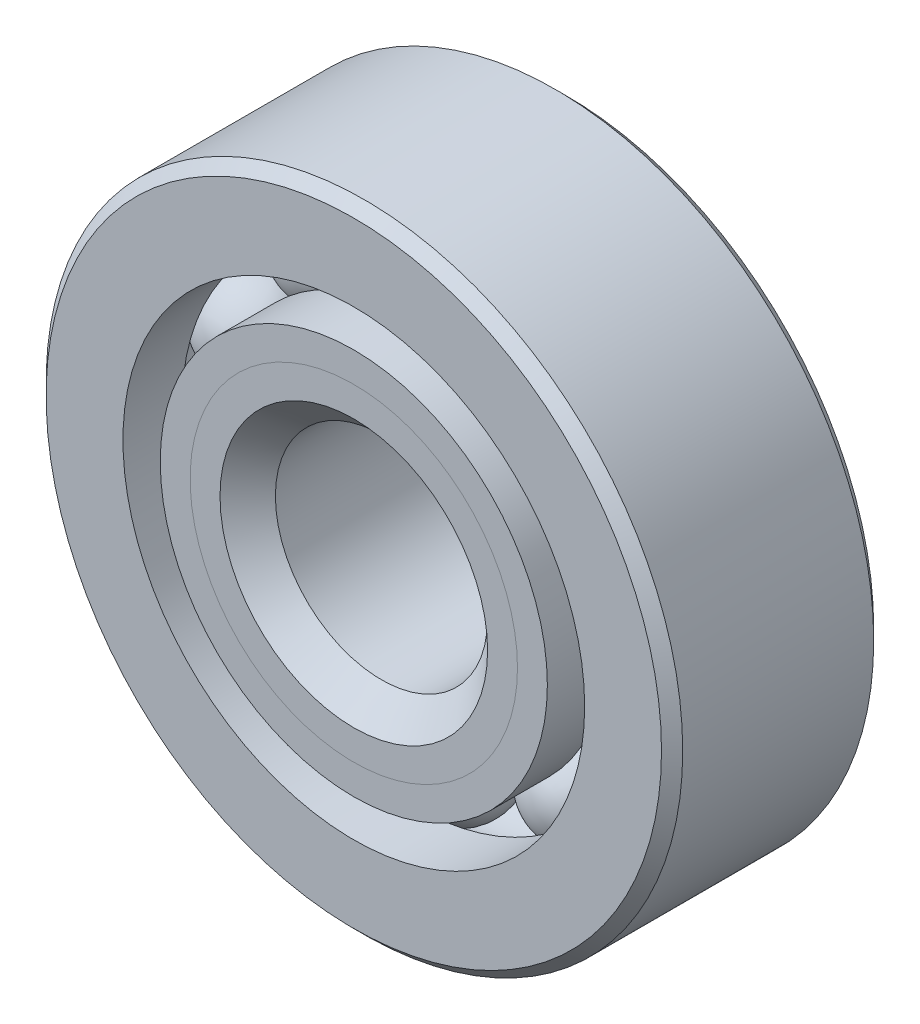
SolidWorks part; units mm, degrees
ref_plane "Front Plane" through (0, 0, 0) normal (0, 0, 1) x (1, 0, 0)
ref_plane "Top Plane" through (0, 0, 0) normal (0, 1, 0) x (1, 0, 0)
ref_plane "Right Plane" through (0, 0, 0) normal (1, 0, 0) x (0, 0, -1)
sketch "Sketch1" plane through (0, 0, 0) normal (1, 0, 0) x (0, 0, -1)
  line L0 (-4.7625, 0) -> (4.7625, 0) construction
  line L1 (0, 14.2875) -> (0, -14.2875) construction
  line L2 (4.2863, 14.2875) -> (-4.2863, 14.2875)
  line L3 (-4.2863, 14.2875) -> (-4.7625, 13.8113)
  line L4 (-4.7625, 13.8113) -> (-4.7625, 10.3624)
  line L5 (-4.7625, 10.3624) -> (-2.1167, 10.3624)
  line L6 (4.7625, 10.3624) -> (2.1167, 10.3624)
  line L7 (4.7625, 13.8113) -> (4.7625, 10.3624)
  line L8 (4.2863, 14.2875) -> (4.7625, 13.8113)
  line L9 (0, 14.2875) -> (0, 9.525) construction
  line L10 (0, 9.525) -> (0, 4.7625) construction
  arc A0 (-2.1167, 10.3624) -> (2.1167, 10.3624) centre (0, 9.525) cw
  point P14 (0, 4.7625)
  dimension "Width" = 9.525
  dimension "OD" = 28.575
  dimension "D1" = 45
  dimension "D2" = 0.4763
  dimension "D3" = 4.2333
  dimension "D4" = 0.8374
revolve "Revolve1" add sketch "Sketch1" angle 360 about L0
sketch "Sketch2" plane through (0, 0, 0) normal (1, 0, 0) x (0, 0, -1)
  line L0 (-4.7625, 8.6876) -> (-2.1167, 8.6876)
  line L1 (-4.7625, 13.8113) -> (-4.7625, -13.8113) construction
  line L2 (-4.7625, 8.6876) -> (-4.7625, 7.3466)
  line L3 (-4.7625, 7.3466) -> (-3.4215, 6.0056)
  line L4 (-3.4215, 6.0056) -> (0, 6.0056)
  line L5 (0, 14.2875) -> (0, -14.2875) construction
  line L6 (0, 6.0056) -> (0, 7.2487)
  line L7 (0, 7.2487) -> (0, 4.7625) construction
  line L8 (-4.7625, 8.6876) -> (-4.7625, 6.0056) construction
  line L9 (-4.7625, 6.0056) -> (-3.4215, 6.0056) construction
  arc A0 (-2.1167, 8.6876) -> (0, 7.2487) centre (0, 9.525) ccw
  arc A1 (2.1167, 10.3624) -> (-2.1167, 10.3624) centre (0, 9.525) ccw construction
  circle A2 centre (0, 9.525) radius 2.2763 construction
  dimension "D1" = 45
revolve "Revolve2" add sketch "Sketch2" angle 360 about L0
sketch "Sketch3" plane through (0, 0, 0) normal (1, 0, 0) x (0, 0, -1)
  line L0 (-4.7625, 7.3466) -> (-3.4215, 6.0056)
  line L1 (-3.4215, 6.0056) -> (0, 6.0056)
  line L2 (0, 6.0056) -> (0, 7.2487)
  line L3 (-4.7625, 7.3466) -> (-4.7625, 6.0056)
  line L4 (-4.7625, 8.6876) -> (-4.7625, 6.0056) construction
  line L5 (-4.7625, 6.0056) -> (-3.5194, 4.7625)
  line L6 (-3.5194, 4.7625) -> (4.2863, 4.7625)
  line L7 (4.2863, 14.2875) -> (4.2863, -14.2875) construction
  line L8 (4.2863, 4.7625) -> (4.7625, 5.2387)
  line L9 (4.7625, -13.8113) -> (4.7625, 13.8113) construction
  line L10 (4.7625, 5.2387) -> (4.7625, 8.6876)
  line L11 (4.7625, 8.6876) -> (2.1167, 8.6876)
  line L13 (4.2863, 14.2875) -> (4.7625, 13.8113) construction
  circle A0 centre (0, 9.525) radius 2.2763 construction
  arc A1 (2.1167, 8.6876) -> (0, 7.2487) centre (0, 9.525) cw
revolve "Revolve3" add sketch "Sketch3" angle 360 about L0
sketch "Sketch4" plane through (0, 0, 0) normal (1, 0, 0) x (0, 0, -1)
  line L0 (-2.2763, 9.525) -> (2.2763, 9.525)
  circle A1 centre (0, 9.525) radius 2.2763 construction
  arc A2 (-2.2763, 9.525) -> (2.2763, 9.525) centre (0, 9.525) cw
  arc A3 (2.1167, 10.3624) -> (-2.1167, 10.3624) centre (0, 9.525) ccw construction
revolve "Revolve4" add sketch "Sketch4" angle 360 about L0
ref_axis "Axis1" through (0, 0, -4.7625) along (0, 0, 1)
pattern_circular "CirPattern1" count 10 every 36 about axis through (0, 0, -4.7625) along (0, 0, 1) of bodies 104
equation "\"D2@Sketch1\" = \"Width@Sketch1\"*.05"
equation "\"D3@Sketch1\" = \"Width@Sketch1\"/2.25"
equation "\"D4@Sketch1\" = (((\"OD@Sketch1\"-\"Width@Sketch1\")/2)/3.25)/3.5"
equation "\"D2@CirPattern1\" = 360/\"Balls@CirPattern1\""
